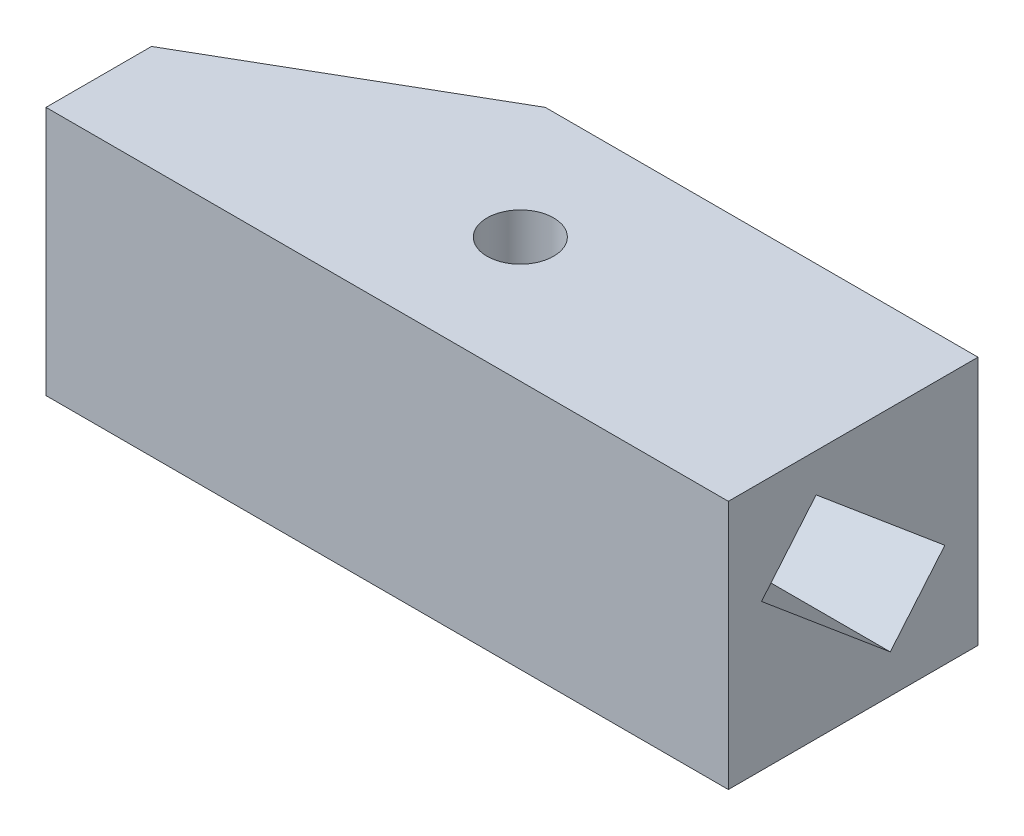
SolidWorks part; units mm, degrees
ref_plane "Спереди" through (0, 0, 0) normal (0, 0, 1) x (1, 0, 0)
ref_plane "Сверху" through (0, 0, 0) normal (0, 1, 0) x (1, 0, 0)
ref_plane "Справа" through (0, 0, 0) normal (1, 0, 0) x (0, 0, -1)
sketch "Эскиз1" plane through (0, 0, 0) normal (0, 1, 0) x (1, 0, 0)
  line L0 (-20, -15) -> (-35, -15)
  line L1 (-20, -15) -> (20, -15)
  line L2 (-35, -15) -> (-35, 15)
  line L3 (-20, 15) -> (20, 15)
  line L4 (20, -15) -> (20, 15)
  line L5 (-20, -15) -> (20, 15) construction
  line L6 (-20, 15) -> (20, -15) construction
  line L7 (-35, 15) -> (-20, 15)
  point P0 (0, 0)
  dimension "D1" = 40
  dimension "D2" = 30
  dimension "D3" = 15
extrude "Бобышка-Вытянуть1" add sketch "Эскиз1" along normal blind 30
sketch "Эскиз2" plane through (0, 30, 0) normal (0, 1, 0) x (1, 0, 0)
  line L0 (-20, -15) -> (-20, 15) construction
  circle A0 centre (-20, 0) radius 4
  dimension "D1" = 15
extrude "Вырез-Вытянуть1" cut sketch "Эскиз2" against normal through all
sketch "Эскиз5" plane through (20, 0, 0) normal (1, 0, 0) x (0, 0, -1)
  line L0 (0, 30) -> (0, 0) construction
  line L1 (-15, 30) -> (15, 0) construction
  line L2 (-15, 0) -> (15, 0) construction
  line L4 (4.4588, 4.601) -> (11.0153, 12.4147)
  line L5 (4.4588, 4.601) -> (-11.0153, 17.5853)
  line L6 (-11.0153, 17.5853) -> (-4.4588, 25.399)
  line L7 (11.0153, 12.4147) -> (-4.4588, 25.399)
  line L8 (4.4588, 4.601) -> (-4.4588, 25.399) construction
  line L9 (-11.0153, 17.5853) -> (11.0153, 12.4147) construction
  point P5 (0, 15)
  point P6 (0, 15)
  dimension "D1" = 20.2
  dimension "D2" = 10.2
  dimension "D3" = 40
extrude "Вырез-Вытянуть4" cut sketch "Эскиз5" against normal blind 25
sketch "Sketch1" plane through (-35, 0, 0) normal (-1, 0, 0) x (0, 0, 1)
  line L0 (0, 30) -> (0, 0) construction
  line L1 (-15, 30) -> (15, 30) construction
  line L3 (-15, 0) -> (15, 0)
  line L4 (-15, 0) -> (-15, 30)
  line L5 (-15, 30) -> (15, 30)
  line L6 (15, 0) -> (15, 30)
  line L7 (-15, 0) -> (15, 30) construction
  line L8 (-15, 30) -> (15, 0) construction
  point P5 (0, 15)
extrude "Boss-Extrude1" add sketch "Sketch1" along normal blind 27
chamfer "Chamfer1" distance 30 angle 30 1 edges at (-62, 15, -15) first distance on face at (-21, 15, -15)
